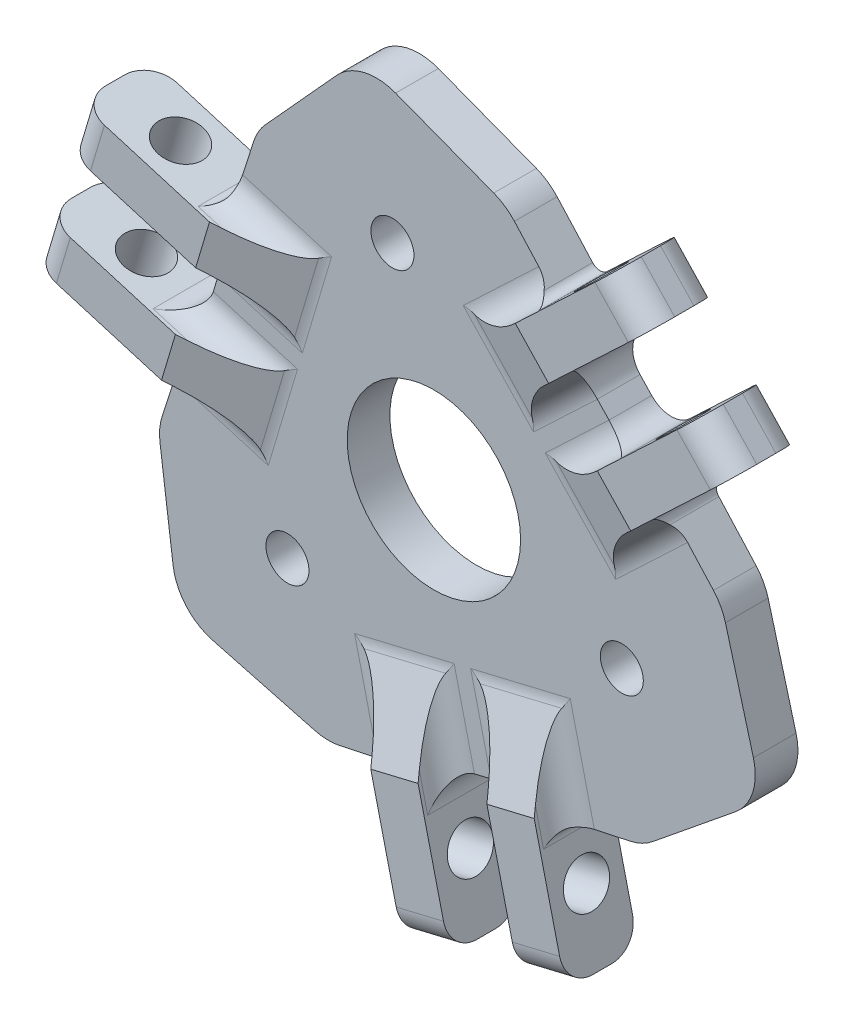
SolidWorks part; units mm, degrees
note: The reader was unsure of these and kept them because the rebuilt part matched: shared geometry of "Sketch4<2>".
ref_plane "Front" through (0, 0, 0) normal (0, 0, 1) x (1, 0, 0)
ref_plane "Top" through (0, 0, 0) normal (0, 1, 0) x (1, 0, 0)
ref_plane "Right" through (0, 0, 0) normal (1, 0, 0) x (0, 0, -1)
sketch "Sketch1" plane through (0, 0, 0) normal (0, 0, 1) x (1, 0, 0)
  line L9 (15.3473, 31.211) -> (8.0515, 33.9989)
  line L10 (3.6638, 32.953) -> (-1.6531, 27.1039)
  line L11 (-2.5002, 25.6411) -> (-9.3254, 4.4787)
  line L12 (-9.4846, 2.7307) -> (-8.5074, -4.7187)
  line L13 (-5.5657, -8.0651) -> (2.031, -10.0776)
  line L14 (3.8955, -10.1217) -> (25.4851, -5.4837)
  line L15 (27.1669, -4.6777) -> (33.3296, 0.3283)
  line L16 (34.6684, 4.4793) -> (32.5917, 12.1426)
  line L17 (31.6977, 13.7794) -> (16.8863, 30.1575)
  line L27 (15.3473, 31.211) -> (8.0515, 33.9989)
  line L28 (3.6638, 32.953) -> (-1.6531, 27.1039)
  line L29 (-2.5002, 25.6411) -> (-9.3254, 4.4787)
  line L30 (-9.4846, 2.7307) -> (-8.5074, -4.7187)
  line L31 (-5.5657, -8.0651) -> (2.031, -10.0776)
  line L32 (3.8955, -10.1217) -> (25.4851, -5.4837)
  line L33 (27.1669, -4.6777) -> (33.3296, 0.3283)
  line L34 (34.6684, 4.4793) -> (32.5917, 12.1426)
  line L35 (31.6977, 13.7794) -> (16.8863, 30.1575)
  circle A0 centre (24.8798, 5.3449) radius 1.6 construction
  circle A1 centre (7.8111, 24.219) radius 1.6 construction
  circle A2 centre (0, 0) radius 1.6 construction
  circle A3 centre (24.8798, 5.3449) radius 1.6
  circle A4 centre (7.8111, 24.219) radius 1.6
  circle A5 centre (0, 0) radius 1.6
  circle A6 centre (10.897, 9.8546) radius 25.6921 construction
  arc A17 (8.0515, 33.9989) -> (3.6638, 32.953) centre (6.6237, 30.2624) ccw
  circle A27 centre (10.897, 9.8546) radius 6.45
  arc A28 (-1.6531, 27.1039) -> (-2.5002, 25.6411) centre (1.3067, 24.4133) ccw
  arc A29 (-9.3254, 4.4787) -> (-9.4846, 2.7307) centre (-5.5185, 3.2509) ccw
  arc A30 (-8.5074, -4.7187) -> (-5.5657, -8.0651) centre (-4.5414, -4.1985) ccw
  arc A31 (2.031, -10.0776) -> (3.8955, -10.1217) centre (3.0553, -6.211) ccw
  arc A32 (25.4851, -5.4837) -> (27.1669, -4.6777) centre (24.6449, -1.5729) ccw
  arc A33 (33.3296, 0.3283) -> (34.6684, 4.4793) centre (30.8076, 3.4331) ccw
  arc A34 (32.5917, 12.1426) -> (31.6977, 13.7794) centre (28.731, 11.0964) ccw
  arc A35 (16.8863, 30.1575) -> (15.3473, 31.211) centre (13.9195, 27.4745) ccw
  arc A36 (8.0515, 33.9989) -> (3.6638, 32.953) centre (6.6237, 30.2624) ccw
  arc A37 (-1.6531, 27.1039) -> (-2.5002, 25.6411) centre (1.3067, 24.4133) ccw
  arc A38 (-9.3254, 4.4787) -> (-9.4846, 2.7307) centre (-5.5185, 3.2509) ccw
  arc A39 (-8.5074, -4.7187) -> (-5.5657, -8.0651) centre (-4.5414, -4.1985) ccw
  arc A40 (2.031, -10.0776) -> (3.8955, -10.1217) centre (3.0553, -6.211) ccw
  arc A41 (25.4851, -5.4837) -> (27.1669, -4.6777) centre (24.6449, -1.5729) ccw
  arc A42 (33.3296, 0.3283) -> (34.6684, 4.4793) centre (30.8076, 3.4331) ccw
  arc A43 (32.5917, 12.1426) -> (31.6977, 13.7794) centre (28.731, 11.0964) ccw
  arc A44 (16.8863, 30.1575) -> (15.3473, 31.211) centre (13.9195, 27.4745) ccw
  dimension "D2" = 12.9
  dimension "D1" = 0
extrude "Boss-Extrude1" add sketch "Sketch1" along normal blind 3.175
sketch "Sketch2" plane through (0, 0, 3.175) normal (0, 0, 1) x (1, 0, 0)
  circle A8 centre (18.3093, 11.6215) radius 1.51 construction
  circle A9 centre (9.13, 17.267) radius 1.51 construction
  circle A10 centre (3.4846, 8.0877) radius 1.51 construction
  circle A11 centre (12.6639, 2.4423) radius 1.51 construction
  circle A12 centre (18.3093, 11.6215) radius 1.51
  circle A13 centre (9.13, 17.267) radius 1.51
  circle A14 centre (3.4846, 8.0877) radius 1.51
  circle A15 centre (12.6639, 2.4423) radius 1.51
extrude "Cut-Extrude1" [suppressed] cut sketch "Sketch2" against normal through all
ref_plane "Plane1" through (0.4496, -0.4753, 0) normal (0.6872, -0.7265, 0) x (-0.7265, -0.6872, 0)
sketch "Sketch4" plane through (0.4496, -0.4753, 0) normal (0.6872, -0.7265, 0) x (-0.7265, -0.6872, 0)
  line L0 (-31.7213, 0) -> (-31.7213, -3.175)
  line L1 (-31.7213, -5.425) -> (-41.8813, -5.425)
  line L2 (-41.8813, -5.425) -> (-41.8813, 0)
  line L3 (-41.8813, 0) -> (-31.7213, 0)
  line L4 (-32.9913, -3.175) -> (-32.9913, 0) construction
  line L6 (-32.9913, 0) -> (-41.8813, 0) construction
  line L7 (-32.9913, 0) -> (-32.9913, -5.425) construction
  line L8 (-32.9913, -5.425) -> (-41.8813, -5.425) construction
  line L9 (-41.8813, 0) -> (-41.8813, -5.425) construction
  line L10 (-36.8013, 0) -> (-36.8013, -5.425) construction
  line L11 (-31.7213, -5.425) -> (-25.5395, -3.175)
  line L12 (-25.5395, -3.175) -> (-31.7213, -3.175)
  line L13 (-32.5973, 0) -> (-32.9923, 0) construction
  line L14 (-32.4968, -3.175) -> (-32.0216, -3.175) construction
  circle A0 centre (-36.8013, -2.7125) radius 1.675
  point P11 (-32.9913, -2.7125)
  dimension "D1" = 3.35
  dimension "D4" = 2.25
  dimension "D2" = 3.81
  dimension "D3" = 1.27
  dimension "D5" = 20
extrude "Boss-Extrude3" add sketch "Sketch4" along normal mid plane 12.5
extrude "Cut-Extrude2" cut sketch "Sketch4<2>" against normal mid plane 5.2625
sketch "Sketch4<2>" plane through (0.4496, -0.4753, 0) normal (0.6872, -0.7265, 0) x (-0.7265, -0.6872, 0) same geometry as "Sketch4"
fillet "Fillet1" radius 2 6 edges at (19.441, 21.1106, 3.175) (23.0573, 17.2875, 3.175) (25.8653, 14.9624, 3.175) (22.0552, 13.849, 3.175) (17.3772, 24.1397, 3.175) (15.9521, 20.3011, 3.175)
fillet "Fillet2" radius 2 2 edges at (25.3028, 19.4115, 2.5875) (21.6865, 23.2346, 2.5875)
fillet "Fillet3" radius 2 4 edges at (27.8241, 31.5309, 0) (33.9272, 25.0788, 0) (33.9272, 25.0788, 5.425) (27.8241, 31.5309, 5.425)
pattern_circular "CirPattern2" count 3 over 360 about axis through (10.897, 9.8546, 0) along (0, 0, 1) of "Cut-Extrude2", "Boss-Extrude3", "Fillet1", "Fillet3", "Fillet2"
fillet "Fillet5" radius 0.75 6 edges at (28.4321, 17.3904, 2.5875) (20.0457, 26.6638, 2.5875) (-3.9518, 21.1401, 2.5875) (-7.7897, 9.2405, 2.5875) (20.8798, -6.473, 2.5875) (8.6555, -9.0991, 2.5875)
